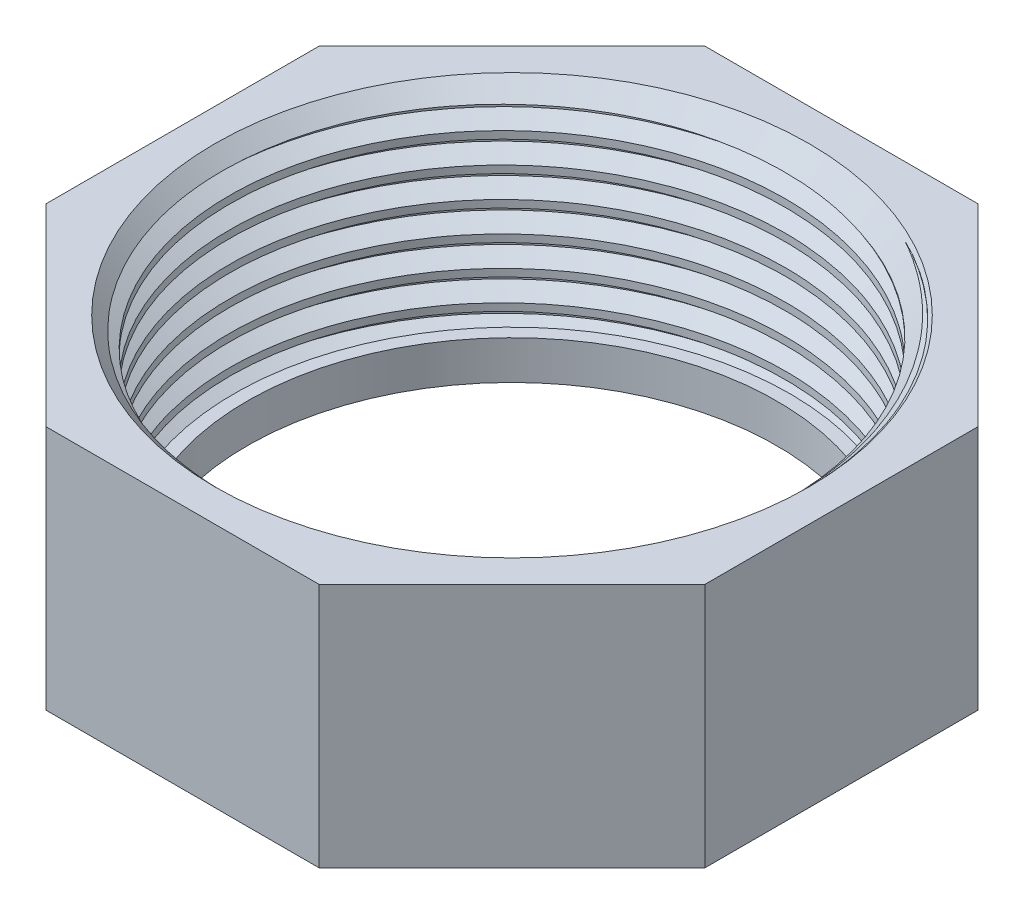
SolidWorks part; units mm, degrees
ref_plane "Plano frontal" through (0, 0, 0) normal (0, 0, 1) x (1, 0, 0)
ref_plane "Plano superior" through (0, 0, 0) normal (0, 1, 0) x (1, 0, 0)
ref_plane "Plano direito" through (0, 0, 0) normal (1, 0, 0) x (0, 0, -1)
sketch "Esboço1" plane through (0, 0, 0) normal (0, 1, 0) x (1, 0, 0)
  line L1 (10.5624, -25.5) -> (25.5, -10.5624)
  line L2 (25.5, -10.5624) -> (25.5, 10.5624)
  line L3 (25.5, 10.5624) -> (10.5624, 25.5)
  line L4 (10.5624, 25.5) -> (-10.5624, 25.5)
  line L5 (-10.5624, 25.5) -> (-25.5, 10.5624)
  line L6 (-25.5, 10.5624) -> (-25.5, -10.5624)
  line L7 (-25.5, -10.5624) -> (-10.5624, -25.5)
  line L8 (-10.5624, -25.5) -> (10.5624, -25.5)
  circle A0 centre (0, 0) radius 25.5 construction
  circle A1 centre (0, 0) radius 20.5
  dimension "D2" = 41
  dimension "D1" = 51
extrude "Ressalto-extrusão1" add sketch "Esboço1" along normal blind 19
sketch "Esboço2" plane through (0, 19, 0) normal (0, 1, 0) x (1, 0, 0)
  circle A0 centre (0, 0) radius 21.5
  dimension "D1" = 43
extrude "Corte-extrusão1" cut sketch "Esboço2" against normal blind 16
chamfer "Chanfro1" distance 1.5 angle 45 1 edges at (0, 19, 21.5)
thread "Rosca1" pitch 2.3091 method cut profile "Perfil da rosca1" start angle 0, offset 3, length 0, pitch 2.3091, diameter 43
ref_plane "Plano1" through (-21.5, 20.5, 0) normal (0, 0, 1) x (-1, 0, 0)
sketch "Perfil da rosca1" plane through (-21.5, 20.5, 0) normal (0, 0, 1) x (-1, 0, 0)
  line L0 (0, 0) -> (0, 2.3091) construction
  line L1 (0, 0) -> (1.2498, 0.7216)
  line L2 (1.2498, 0.7216) -> (1.2498, 1.0102)
  line L3 (1.2498, 1.0102) -> (0, 1.7318)
  line L4 (1.2498, 0.8659) -> (0, 0.8659) construction
  line L11 (0, 0) -> (0, 1.7318)
  point P2 (0, 0)
  dimension "Pitch" = 2.3091
  dimension "Profile_Angle" = 60
  dimension "Profile_Land" = 0.2886
  dimension "Profile_Height" = 1.2498
